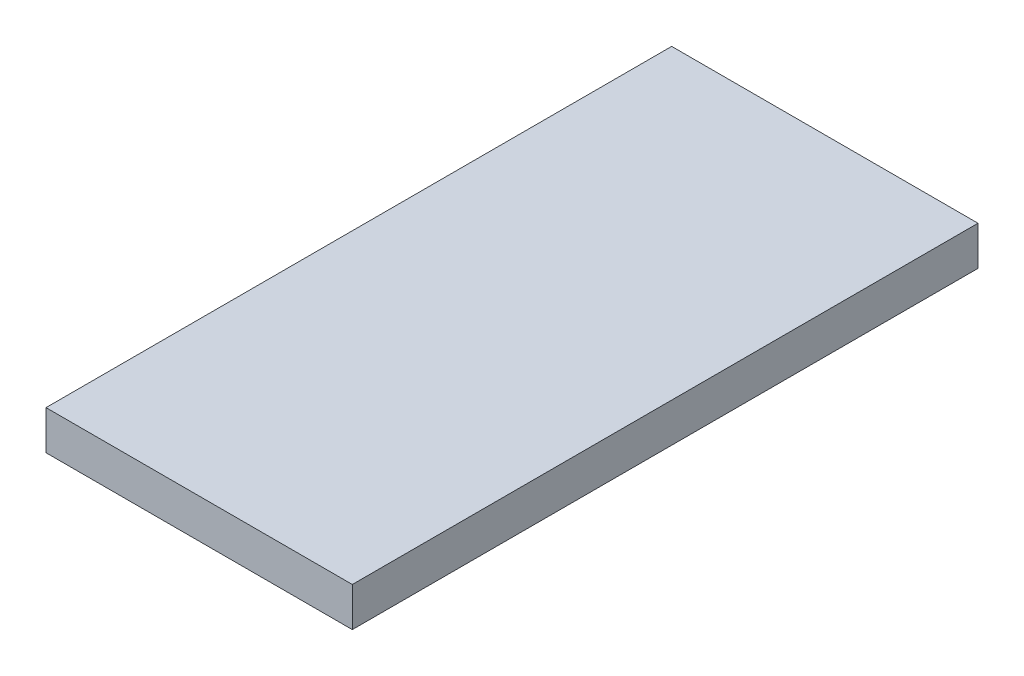
SolidWorks part; units mm, degrees
ref_plane "Front Plane" through (0, 0, 0) normal (0, 0, 1) x (1, 0, 0)
ref_plane "Top Plane" through (0, 0, 0) normal (0, 1, 0) x (1, 0, 0)
ref_plane "Right Plane" through (0, 0, 0) normal (1, 0, 0) x (0, 0, -1)
sketch "Sketch1" plane through (0, 0, 0) normal (0, 1, 0) x (1, 0, 0)
  line L1 (-74.6125, -152.4) -> (74.6125, -152.4)
  line L2 (-74.6125, -152.4) -> (-74.6125, 152.4)
  line L3 (-74.6125, 152.4) -> (74.6125, 152.4)
  line L4 (74.6125, -152.4) -> (74.6125, 152.4)
  line L5 (-74.6125, -152.4) -> (74.6125, 152.4) construction
  line L6 (-74.6125, 152.4) -> (74.6125, -152.4) construction
  point P0 (0, 0)
  dimension "D1" = 149.225
  dimension "D2" = 304.8
extrude "Boss-Extrude1" add sketch "Sketch1" along normal blind 19.05
